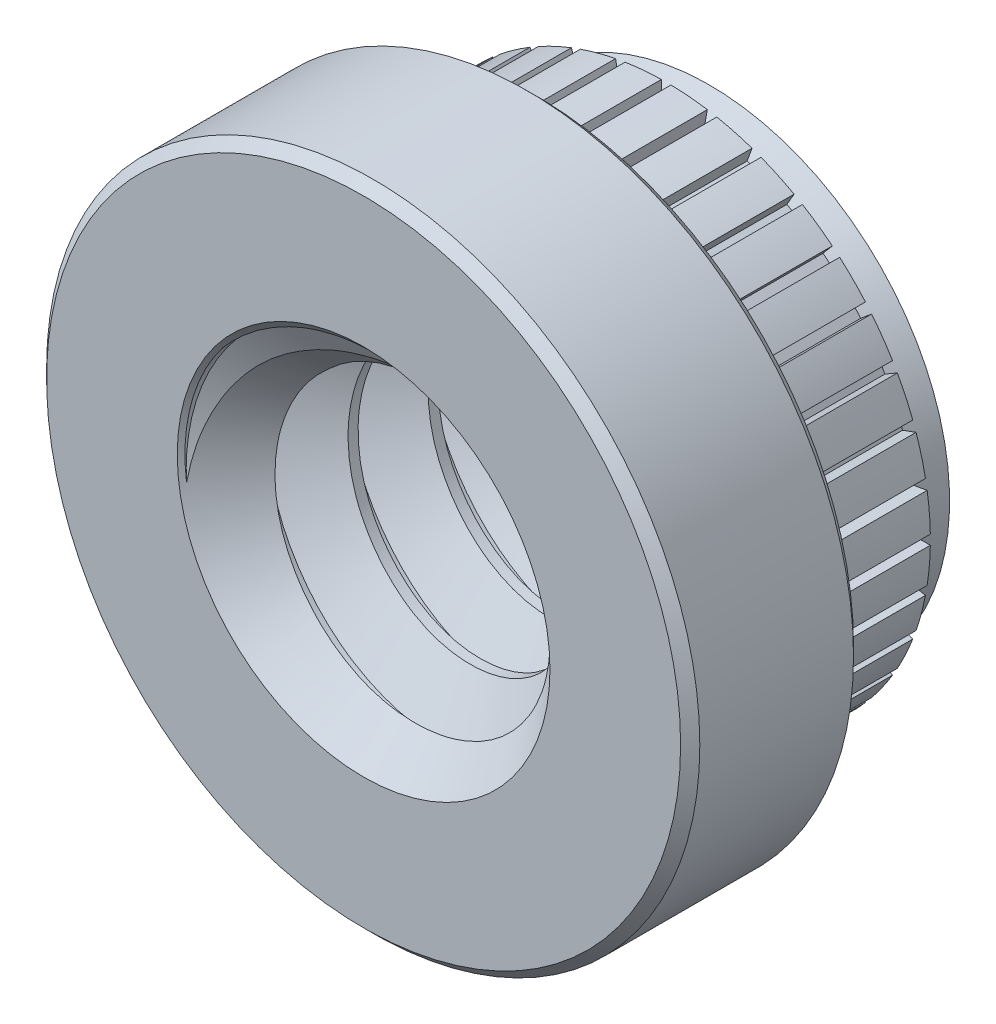
SolidWorks part; units mm, degrees
ref_plane "Front Plane" through (0, 0, 0) normal (0, 0, 1) x (1, 0, 0)
ref_plane "Top Plane" through (0, 0, 0) normal (0, 1, 0) x (1, 0, 0)
ref_plane "Right Plane" through (0, 0, 0) normal (1, 0, 0) x (0, 0, -1)
sketch "Sketch1" plane through (0, 0, 0) normal (0, 0, 1) x (1, 0, 0)
  circle A0 centre (0, 0) radius 4.318
  dimension "A" = 8.636
extrude "Extrude1" add sketch "Sketch1" against normal blind 2.286
sketch "Sketch15" plane through (0, 0, -2.286) normal (0, 0, -1) x (-1, 0, 0)
  circle A0 centre (0, 0) radius 3.175
  dimension "hole dia" = 6.35
sketch "Sketch2" plane through (0, 0, -2.286) normal (0, 0, -1) x (-1, 0, 0)
  circle A0 centre (0, 0) radius 3.4925
  dimension "D1" = 6.985
extrude "Extrude2" add sketch "Sketch2" along normal blind 2.286
sketch "Sketch3" plane through (0, 0, -4.572) normal (0, 0, -1) x (-1, 0, 0)
  line L0 (0, 3.302) -> (0, 4.318)
  circle A1 centre (0, 0) radius 4.318 construction
  circle A2 centre (0, 0) radius 3.302
  circle A3 centre (0, 0) radius 3.302 construction
  dimension "D1" = 0.1905
extrude "Cut-Extrude-Thin1" cut sketch "Sketch3" against normal up to surface (2.286 mm away) thin up to face at (4.318, 0, -2.286) thin type mid plane wall 0.127
pattern_circular "CirPattern1" count 36 over 360 about axis through (0, 0, 0) along (0, 0, 1) of "Cut-Extrude-Thin1"
sketch "Sketch5" plane through (0, 0, -4.572) normal (0, 0, -1) x (-1, 0, 0)
  circle A0 centre (0, 0) radius 4.318 construction
  circle A3 centre (0, 0) radius 3.175
  dimension "C" = 6.35
extrude "Cut-Extrude1" cut sketch "Sketch5" against normal blind 0.5715 draft 20 flip side to cut draft outward yes
chamfer "Chamfer2" distance 0.127 angle 45 2 edges at (4.318, 0, 0) (4.318, 0, -2.286)
sketch "Sketch7" plane through (0, 0, 0) normal (0, 0, 1) x (1, 0, 0)
  circle A0 centre (0, 0) radius 2.413
  dimension "Thread Od" = 4.826
extrude "Cut-Extrude3" cut sketch "Sketch7" against normal through all
sketch "Sketch8" plane through (0, 0, -4.572) normal (0, 0, -1) x (-1, 0, 0)
  circle A0 centre (0, 0) radius 2.413 construction
  circle A1 centre (0, 0) radius 2.413
curve "Helix/Spiral1" pitch 1.0583 height 7.747 turns 7.32 parameters "pitch"=1.0583
sketch "Sketch9" plane through (0, 0, 0) normal (1, 0, 0) x (0, 0, -1)
  line L0 (5.498, 2.413) -> (5.1012, 1.7256)
  line L1 (5.1012, 1.7256) -> (4.9689, 1.7256)
  line L2 (4.9689, 1.7256) -> (4.572, 2.413)
  line L3 (5.498, 2.413) -> (4.572, 2.413)
  line L4 (5.035, 2.413) -> (5.035, 1.7256) construction
  line L5 (5.2996, 2.0693) -> (4.7704, 2.0693) construction
  line L6 (4.572, -2.413) -> (4.572, 2.413) construction
  dimension "D1" = 60
  dimension "D2" = 0.1323
  dimension "D3" = 0.5292
sweep "Sweep1" add profiles "Sketch9" path "Helix/Spiral1"
sketch "Sketch10" plane through (0, 0, 0) normal (0, 0, 1) x (1, 0, 0)
  circle A0 centre (0, 0) radius 4.318 construction
  circle A1 centre (0, 0) radius 4.318
extrude "Cut-Extrude4" cut sketch "Sketch10" along normal through all
sketch "Sketch11" plane through (0, 0, -4.572) normal (0, 0, -1) x (-1, 0, 0)
  circle A1 centre (0, 0) radius 3.175 construction
  circle A2 centre (0, 0) radius 3.175
extrude "Cut-Extrude5" cut sketch "Sketch11" along normal through all
sketch "Sketch13" plane through (0, 0, 0) normal (0, 0, 1) x (1, 0, 0)
  circle A2 centre (0, 0) radius 2.4638
  circle A3 centre (0, 0) radius 2.4638
  dimension "D1" = 0.0508
extrude "Cut-Extrude6" cut sketch "Sketch13" against normal through all draft 45
sketch "Sketch14" plane through (0, 0, -4.572) normal (0, 0, -1) x (-1, 0, 0)
  circle A2 centre (0, 0) radius 2.4638
  circle A3 centre (0, 0) radius 2.4638
  dimension "D1" = 0.0508
extrude "Cut-Extrude7" cut sketch "Sketch14" against normal through all draft 45
equation "\"D3@Helix/Spiral1\" = \"B@Extrude1\"+\"panel min.@Extrude2\"+.125"
equation "\"D2@Sketch9\" = \"pitch@Helix/Spiral1\"*.125"
equation "\"D3@Sketch9\" = \"pitch@Helix/Spiral1\"*.50"
equation "\"D1@Sketch2\" = \"hole dia@Sketch15\"+.025"
equation "\"D1@Cut-Extrude1\" = \"panel min.@Extrude2\"*.25"
